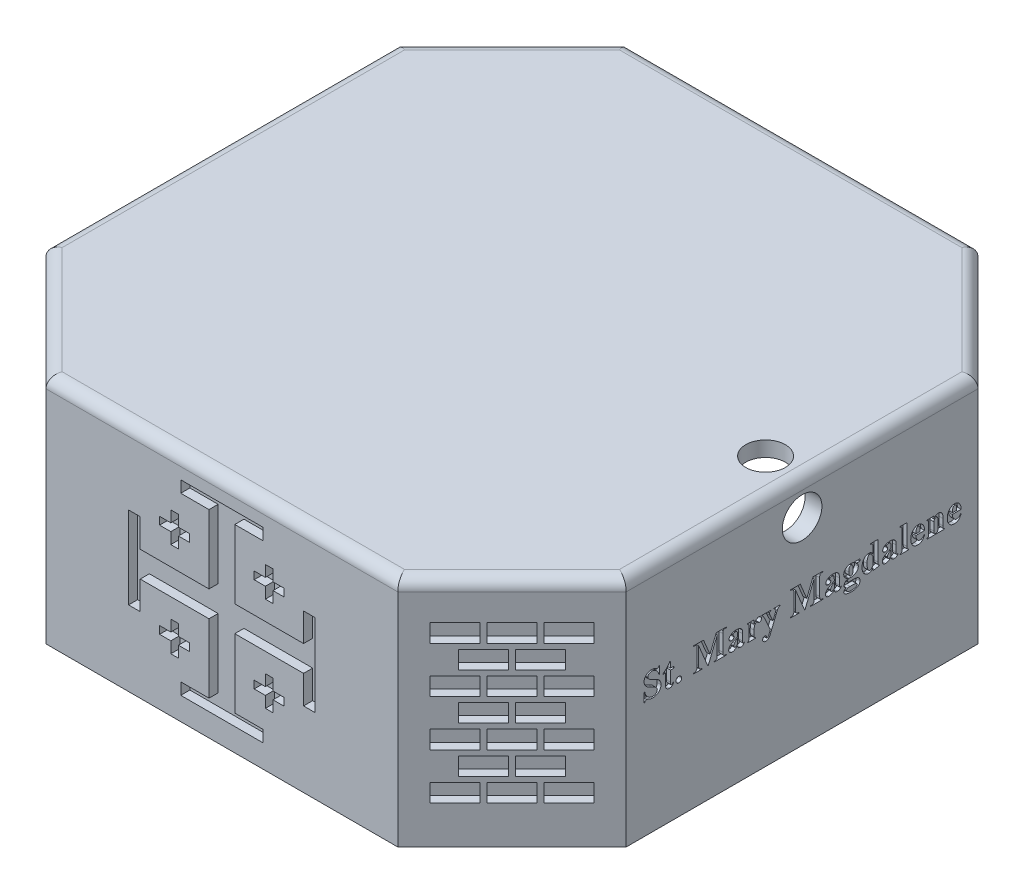
SolidWorks part; units mm, degrees
note: '?' marks a value the reader was unsure of.
ref_plane "Front Plane" through (0, 0, 0) normal (0, 0, 1) x (1, 0, 0)
ref_plane "Top Plane" through (0, 0, 0) normal (0, 1, 0) x (1, 0, 0)
ref_plane "Right Plane" through (0, 0, 0) normal (1, 0, 0) x (0, 0, -1)
sketch "Sketch1" plane through (0, 0, 0) normal (0, 1, 0) x (1, 0, 0)
  line L1 (0, 0) -> (38.1, 0)
  line L2 (0, 0) -> (0, 38.1)
  line L3 (0, 38.1) -> (38.1, 38.1)
  line L4 (38.1, 0) -> (38.1, 38.1)
  dimension "D1" = 38.1
extrude "Boss-Extrude1" add sketch "Sketch1" along normal blind 15.2575
sketch "Sketch2" plane through (0, 15.2575, 0) normal (0, 1, 0) x (1, 0, 0)
  line L0 (0, 19.05) -> (38.1, 19.05) construction
  line L1 (0, 38.1) -> (0, 0) construction
  line L2 (38.1, 0) -> (38.1, 38.1) construction
  line L15 (38.1, 30.6) -> (30.6, 38.1)
  line L33 (38.1, 7.5) -> (30.6, 0)
  line L34 (7.5, 0) -> (0, 7.5)
  line L35 (7.5, 38.1) -> (0, 30.6)
  line L36 (38.1, 7.5) -> (38.1, 0)
  line L37 (38.1, 0) -> (30.6, 0)
  line L38 (38.1, 30.6) -> (38.1, 38.1)
  line L39 (38.1, 38.1) -> (30.6, 38.1)
  line L40 (7.5, 38.1) -> (0, 38.1)
  line L41 (0, 38.1) -> (0, 30.6)
  line L42 (0, 7.5) -> (0, 0)
  line L43 (0, 0) -> (7.5, 0)
  dimension "D1" = 7.5
extrude "Cut-Extrude1" cut sketch "Sketch2" against normal through all
ref_plane "Plane1" through (30.6, 0, 0) normal (1, 0, 0) x (0, 1, 0)
ref_plane "Plane2" through (0, 0, -19.05) normal (0, 0, 1) x (1, 0, 0)
ref_plane "Plane3" through (19.05, 0, 0) normal (-1, 0, 0) x (0, 0, 1)
sketch "Sketch11" plane through (0, 0, 0) normal (0, -1, 0) x (1, 0, 0)
  line L0 (1.1, -30.1444) -> (7.9556, -37)
  line L1 (7.9556, -37) -> (30.1444, -37)
  line L2 (30.1444, -37) -> (37, -30.1444)
  line L3 (37, -30.1444) -> (37, -7.9556)
  line L4 (37, -7.9556) -> (30.1444, -1.1)
  line L5 (30.1444, -1.1) -> (7.9556, -1.1)
  line L6 (7.9556, -1.1) -> (1.1, -7.9556)
  line L7 (1.1, -7.9556) -> (1.1, -30.1444)
  line L8 (7.5, 0) -> (0, -7.5) construction
  line L10 (1.1, -19.05) -> (0, -19.05) construction
  line L11 (0, -30.6) -> (0, -7.5) construction
  line L14 (19.05, -1.1) -> (19.05, 0) construction
  line L15 (7.5, 0) -> (30.6, 0) construction
  line L18 (37, -19.05) -> (38.1, -19.05) construction
  line L19 (38.1, -7.5) -> (38.1, -30.6) construction
  line L22 (19.05, -37) -> (19.05, -38.1) construction
  line L23 (30.6, -38.1) -> (7.5, -38.1) construction
  dimension "D1" = 1.1
  dimension "D2" = 1.1
extrude "Cut-Extrude5" cut sketch "Sketch11" against normal offset from surface (14.2575 mm away) 1 up to face at (19.05, 15.2575, -19.05)
sketch "Sketch12" plane through (0, 15.2575, 0) normal (0, 1, 0) x (1, 0, 0)
  line L0 (38.1, 19.05) -> (0, 19.05) construction
  line L1 (38.1, 7.5) -> (38.1, 30.6) construction
  line L2 (0, 30.6) -> (0, 7.5) construction
  line L3 (37, 7.9556) -> (37, 30.1444) construction
  line L4 (37, 7.9556) -> (37, 30.1444) construction
  circle A0 centre (35.7, 19.05) radius 1.3
  dimension "D1" = 2.6
extrude "Cut-Extrude6" cut sketch "Sketch12" against normal through all
ref_axis "Axis1" through (19.05, 16.0204, -19.05) along (0, -1, 0)?
sketch "Sketch15" plane through (0, 0, -38.1) normal (0, 0, -1) x (-1, 0, 0)
  line L0 (-19.05, 15.2575) -> (-19.05, 0) construction
  line L1 (-30.6, 15.2575) -> (-7.5, 15.2575) construction
  line L2 (-30.6, 0) -> (-7.5, 0) construction
  line L3 (-19.05, 13.7575) -> (-21.7513, 13.7575)
  line L4 (-21.7513, 13.7575) -> (-21.7513, 12.9911)
  line L5 (-21.7513, 12.9911) -> (-19.8974, 12.9911)
  line L6 (-19.8974, 12.9911) -> (-19.8974, 8.4762)
  line L7 (-19.8974, 8.4762) -> (-24.4123, 8.4762)
  line L8 (-24.4123, 8.4762) -> (-24.4123, 10.3301)
  line L9 (-24.4123, 10.3301) -> (-25.1788, 10.3301)
  line L10 (-25.1788, 10.3301) -> (-25.1788, 7.6288)
  line L11 (-22.1549, 8.4762) -> (-22.1549, 10.7336) construction
  line L12 (-22.1549, 10.7336) -> (-19.8974, 10.7336) construction
  line L13 (-22.4049, 11.7205) -> (-21.9049, 11.7205)
  line L14 (-21.9049, 11.7205) -> (-21.9049, 10.9836)
  line L15 (-21.9049, 10.9836) -> (-21.168, 10.9836)
  line L16 (-21.168, 10.9836) -> (-21.168, 10.4836)
  line L17 (-21.9049, 9.7468) -> (-22.4049, 9.7468)
  line L18 (-21.9049, 10.4836) -> (-21.9049, 9.7468)
  line L19 (-21.168, 10.4836) -> (-21.9049, 10.4836)
  line L20 (-23.1417, 10.4836) -> (-23.1417, 10.9836)
  line L21 (-22.4049, 10.4836) -> (-23.1417, 10.4836)
  line L22 (-22.4049, 9.7468) -> (-22.4049, 10.4836)
  line L23 (-22.4049, 11.7205) -> (-21.9049, 11.7205)
  line L24 (-22.4049, 10.9836) -> (-22.4049, 11.7205)
  line L25 (-23.1417, 10.9836) -> (-22.4049, 10.9836)
  line L26 (-19.8974, 8.4762) -> (-19.05, 7.6288) construction
  line L27 (-12.9212, 7.6288) -> (-12.9212, 10.3301)
  line L28 (-12.9212, 10.3301) -> (-13.6877, 10.3301)
  line L29 (-13.6877, 10.3301) -> (-13.6877, 8.4762)
  line L30 (-13.6877, 8.4762) -> (-18.2026, 8.4762)
  line L31 (-18.2026, 8.4762) -> (-18.2026, 12.9911)
  line L32 (-18.2026, 12.9911) -> (-16.3487, 12.9911)
  line L33 (-16.3487, 12.9911) -> (-16.3487, 13.7575)
  line L34 (-16.3487, 13.7575) -> (-19.05, 13.7575)
  line L35 (-14.9583, 10.9836) -> (-14.9583, 10.4836)
  line L36 (-14.9583, 10.4836) -> (-15.6951, 10.4836)
  line L37 (-15.6951, 10.4836) -> (-15.6951, 9.7468)
  line L38 (-15.6951, 9.7468) -> (-16.1951, 9.7468)
  line L39 (-16.932, 10.4836) -> (-16.932, 10.9836)
  line L40 (-16.1951, 10.4836) -> (-16.932, 10.4836)
  line L41 (-16.1951, 9.7468) -> (-16.1951, 10.4836)
  line L42 (-16.1951, 11.7205) -> (-15.6951, 11.7205)
  line L43 (-16.1951, 10.9836) -> (-16.1951, 11.7205)
  line L44 (-16.932, 10.9836) -> (-16.1951, 10.9836)
  line L45 (-14.9583, 10.9836) -> (-14.9583, 10.4836)
  line L46 (-15.6951, 10.9836) -> (-14.9583, 10.9836)
  line L47 (-15.6951, 11.7205) -> (-15.6951, 10.9836)
  line L48 (-18.2026, 10.7336) -> (-15.9451, 10.7336) construction
  line L49 (-15.9451, 10.7336) -> (-15.9451, 8.4762) construction
  line L50 (-19.05, 1.5) -> (-16.3487, 1.5)
  line L51 (-16.3487, 1.5) -> (-16.3487, 2.2665)
  line L52 (-16.3487, 2.2665) -> (-18.2026, 2.2665)
  line L53 (-18.2026, 2.2665) -> (-18.2026, 6.7813)
  line L54 (-18.2026, 6.7813) -> (-13.6877, 6.7813)
  line L55 (-13.6877, 6.7813) -> (-13.6877, 4.9275)
  line L56 (-13.6877, 4.9275) -> (-12.9212, 4.9275)
  line L57 (-12.9212, 4.9275) -> (-12.9212, 7.6288)
  line L58 (-15.6951, 3.537) -> (-16.1951, 3.537)
  line L59 (-16.1951, 3.537) -> (-16.1951, 4.2739)
  line L60 (-16.1951, 4.2739) -> (-16.932, 4.2739)
  line L61 (-16.932, 4.2739) -> (-16.932, 4.7739)
  line L62 (-16.1951, 5.5108) -> (-15.6951, 5.5108)
  line L63 (-16.1951, 4.7739) -> (-16.1951, 5.5108)
  line L64 (-16.932, 4.7739) -> (-16.1951, 4.7739)
  line L65 (-14.9583, 4.7739) -> (-14.9583, 4.2739)
  line L66 (-15.6951, 4.7739) -> (-14.9583, 4.7739)
  line L67 (-15.6951, 5.5108) -> (-15.6951, 4.7739)
  line L68 (-15.6951, 3.537) -> (-16.1951, 3.537)
  line L69 (-15.6951, 4.2739) -> (-15.6951, 3.537)
  line L70 (-14.9583, 4.2739) -> (-15.6951, 4.2739)
  line L71 (-15.9451, 6.7813) -> (-15.9451, 4.5239) construction
  line L72 (-15.9451, 4.5239) -> (-18.2026, 4.5239) construction
  line L73 (-25.1788, 7.6288) -> (-25.1788, 4.9275)
  line L74 (-25.1788, 4.9275) -> (-24.4123, 4.9275)
  line L75 (-24.4123, 4.9275) -> (-24.4123, 6.7813)
  line L76 (-24.4123, 6.7813) -> (-19.8974, 6.7813)
  line L77 (-19.8974, 6.7813) -> (-19.8974, 2.2665)
  line L78 (-19.8974, 2.2665) -> (-21.7513, 2.2665)
  line L79 (-21.7513, 2.2665) -> (-21.7513, 1.5)
  line L80 (-21.7513, 1.5) -> (-19.05, 1.5)
  line L81 (-23.1417, 4.2739) -> (-23.1417, 4.7739)
  line L82 (-23.1417, 4.7739) -> (-22.4049, 4.7739)
  line L83 (-22.4049, 4.7739) -> (-22.4049, 5.5108)
  line L84 (-22.4049, 5.5108) -> (-21.9049, 5.5108)
  line L85 (-21.168, 4.7739) -> (-21.168, 4.2739)
  line L86 (-21.9049, 4.7739) -> (-21.168, 4.7739)
  line L87 (-21.9049, 5.5108) -> (-21.9049, 4.7739)
  line L88 (-21.9049, 3.537) -> (-22.4049, 3.537)
  line L89 (-21.9049, 4.2739) -> (-21.9049, 3.537)
  line L90 (-21.168, 4.2739) -> (-21.9049, 4.2739)
  line L91 (-23.1417, 4.2739) -> (-23.1417, 4.7739)
  line L92 (-22.4049, 4.2739) -> (-23.1417, 4.2739)
  line L93 (-22.4049, 3.537) -> (-22.4049, 4.2739)
  line L94 (-19.8974, 4.5239) -> (-22.1549, 4.5239) construction
  line L95 (-22.1549, 4.5239) -> (-22.1549, 6.7813) construction
  point P24 (-21.168, 10.7336)
  point P25 (-22.1549, 11.7205)
  point P26 (-19.05, 7.6288)
  point P40 (-22.1549, 10.7336)
  point P57 (-15.9451, 9.7468)
  point P58 (-14.9583, 10.7336)
  point P68 (-15.9451, 10.7336)
  point P86 (-16.932, 4.5239)
  point P87 (-15.9451, 3.537)
  point P97 (-15.9451, 4.5239)
  point P115 (-22.1549, 5.5108)
  point P116 (-23.1417, 4.5239)
  point P126 (-22.1549, 4.5239)
  point P127 (-19.05, 7.6288)
  dimension "D1" = 45
  dimension "D3" = 0.5
  dimension "D4" = 1.5
  dimension "D5" = 1.5
  dimension "D2" = 4
extrude "Cut-Extrude9" cut sketch "Sketch15" against normal blind 0.6 contours L79 L80 L50 L51 L52 L53 L54 L55 L56 L57 L27 L28 L29 L30 L31 L32 L33 L34 L3 L4 L5 L6 L7 L8 L9 L10 L73 L74 L75 L76 L77 L78 | L25 L20 L21 L22 L17 L18 L19 L16 L15 L14 L13 L24 | L47 L42 L43 L44 L39 L40 L41 L38 L37 L36 L35 L46 | L70 L65 L66 L67 L62 L63 L64 L61 L60 L59 L58 L69 | L93 L88 L89 L90 L85 L86 L87 L84 L83 L82 L81 L92
mirror "Mirror3" about plane through (0, 0, -19.05) normal (0, 0, 1) of "Cut-Extrude9"
sketch "Sketch16" plane through (38.1, 0, 0) normal (1, 0, 0) x (0, 0, -1)
  line L0 (7.5, 7.6288) -> (30.6, 7.6288) construction
  line L1 (7.5, 0) -> (7.5, 15.2575) construction
  line L2 (30.6, 0) -> (30.6, 15.2575) construction
  text T0 "St. Mary Magdalene" font "Times New Roman" height 1.6
extrude "Cut-Extrude10" cut sketch "Sketch16" against normal blind 0.25
sketch "Sketch17" plane through (0, 0, 0) normal (-1, 0, 0) x (0, 0, 1)
  line L0 (-19.05, 0) -> (-19.05, 15.2575) construction
  line L1 (-30.6, 0) -> (-7.5, 0) construction
  line L2 (-30.6, 15.2575) -> (-7.5, 15.2575) construction
  line L3 (-18.0272, 12.7575) -> (-20.0728, 12.7575)
  line L4 (-20.0728, 12.7575) -> (-20.0728, 11.5984)
  line L5 (-20.0728, 11.5984) -> (-21.0857, 11.5984)
  line L6 (-21.0857, 11.5984) -> (-21.0857, 12.7575)
  line L7 (-21.0857, 12.7575) -> (-22.3904, 12.7575)
  line L8 (-22.3904, 12.7575) -> (-22.3904, 9.9341)
  line L9 (-22.3904, 9.9341) -> (-20.7476, 9.9341)
  line L10 (-20.7476, 9.9341) -> (-21.6155, 4.1643)
  line L11 (-21.6155, 4.1643) -> (-23.3564, 4.1643)
  line L12 (-23.3564, 4.1643) -> (-23.3564, 2.5)
  line L13 (-23.3564, 2.5) -> (-14.7436, 2.5)
  line L14 (-30.6, 12.7575) -> (-7.5, 12.7575) construction
  line L15 (-30.6, 0) -> (-30.6, 15.2575) construction
  line L16 (-7.5, 0) -> (-7.5, 15.2575) construction
  line L17 (-30.6, 2.5) -> (-7.5, 2.5) construction
  line L20 (-18.0272, 12.7575) -> (-18.0272, 11.5984)
  line L21 (-17.0143, 11.5984) -> (-17.0143, 12.7575)
  line L22 (-18.0272, 11.5984) -> (-17.0143, 11.5984)
  line L23 (-17.0143, 12.7575) -> (-15.7096, 12.7575)
  line L24 (-15.7096, 12.7575) -> (-15.7096, 9.9341)
  line L25 (-15.7096, 9.9341) -> (-17.3524, 9.9341)
  line L26 (-17.3524, 9.9341) -> (-16.4845, 4.1643)
  line L27 (-14.7436, 4.1643) -> (-14.7436, 2.5)
  line L28 (-16.4845, 4.1643) -> (-14.7436, 4.1643)
  line L29 (-17.3524, 9.9341) -> (-17.3524, 11.5984) construction
  line L30 (-17.3524, 11.5984) -> (-17.0143, 11.5984) construction
  point P31 (-19.05, 12.7575)
  point P42 (-19.05, 2.5)
  dimension "D1" = 2.5
  dimension "D2" = 2.5
extrude "Cut-Extrude11" cut sketch "Sketch17" against normal blind 0.6
sketch "Sketch18" plane through (-15.3, 0, -15.3) normal (-0.7071, 0, -0.7071) x (-0.7071, 0, 0.7071)
  line L0 (-28.4361, 3.6728) -> (-28.0948, 3.6728) construction
  line L1 (-30.7441, 3.6728) -> (-28.4361, 3.6728)
  line L2 (-30.7441, 3.6728) -> (-30.7441, 2.5)
  line L3 (-30.7441, 2.5) -> (-28.4361, 2.5)
  line L4 (-28.4361, 3.6728) -> (-28.4361, 2.5)
  line L5 (-28.4361, 3.6728) -> (-28.4361, 4.0141) construction
  line L6 (-32.2441, 2.5) -> (-21.6375, 2.5) construction
  line L7 (-32.2441, 0) -> (-32.2441, 15.2575) construction
  line L8 (-21.6375, 0) -> (-21.6375, 15.2575) construction
  line L9 (-32.2441, 12.7575) -> (-21.6375, 12.7575) construction
  line L10 (-32.2441, 15.2575) -> (-21.6375, 15.2575) construction
  line L11 (-32.2441, 0) -> (-21.6375, 0) construction
  line L12 (-30.7441, 0) -> (-30.7441, 15.2575) construction
  line L13 (-23.1375, 15.2575) -> (-23.1375, 0) construction
  line L14 (-28.0948, 3.6728) -> (-25.7868, 3.6728)
  line L15 (-28.0948, 3.6728) -> (-28.0948, 2.5)
  line L16 (-28.0948, 2.5) -> (-25.7868, 2.5)
  line L17 (-25.7868, 3.6728) -> (-25.7868, 2.5)
  line L18 (-25.7868, 3.6728) -> (-25.4454, 3.6728) construction
  line L19 (-25.7868, 3.6728) -> (-25.7868, 4.0141) construction
  line L20 (-25.4454, 3.6728) -> (-23.1375, 3.6728)
  line L21 (-25.4454, 3.6728) -> (-25.4454, 2.5)
  line L22 (-25.4454, 2.5) -> (-23.1375, 2.5)
  line L23 (-23.1375, 3.6728) -> (-23.1375, 2.5)
  line L24 (-23.1375, 3.6728) -> (-22.7961, 3.6728) construction
  line L25 (-23.1375, 3.6728) -> (-23.1375, 4.0141) construction
  line L26 (-25.6161, 3.6728) -> (-25.6161, 4.0141) construction
  line L27 (-29.4194, 5.1869) -> (-27.1114, 5.1869)
  line L28 (-29.4194, 5.1869) -> (-29.4194, 4.0141)
  line L29 (-29.4194, 4.0141) -> (-27.1114, 4.0141)
  line L30 (-27.1114, 5.1869) -> (-27.1114, 4.0141)
  line L31 (-26.7701, 5.1869) -> (-24.4621, 5.1869)
  line L32 (-26.7701, 5.1869) -> (-26.7701, 4.0141)
  line L33 (-26.7701, 4.0141) -> (-24.4621, 4.0141)
  line L34 (-24.4621, 5.1869) -> (-24.4621, 4.0141)
  line L35 (-28.2654, 3.6728) -> (-28.2654, 4.0141) construction
  line L36 (-27.1114, 5.1869) -> (-26.7701, 5.1869) construction
  line L37 (-30.7441, 6.701) -> (-28.4361, 6.701)
  line L38 (-30.7441, 6.701) -> (-30.7441, 5.5283)
  line L39 (-30.7441, 5.5283) -> (-28.4361, 5.5283)
  line L40 (-28.4361, 6.701) -> (-28.4361, 5.5283)
  line L41 (-28.0948, 6.701) -> (-25.7868, 6.701)
  line L42 (-28.0948, 6.701) -> (-28.0948, 5.5283)
  line L43 (-28.0948, 5.5283) -> (-25.7868, 5.5283)
  line L44 (-25.7868, 6.701) -> (-25.7868, 5.5283)
  line L45 (-25.4454, 6.701) -> (-23.1375, 6.701)
  line L46 (-25.4454, 6.701) -> (-25.4454, 5.5283)
  line L47 (-25.4454, 5.5283) -> (-23.1375, 5.5283)
  line L48 (-23.1375, 6.701) -> (-23.1375, 5.5283)
  line L49 (-28.4361, 6.701) -> (-28.0948, 6.701) construction
  line L50 (-25.7868, 6.701) -> (-25.4454, 6.701) construction
  line L51 (-30.7441, 9.7293) -> (-28.4361, 9.7293)
  line L52 (-30.7441, 9.7293) -> (-30.7441, 8.5565)
  line L53 (-30.7441, 8.5565) -> (-28.4361, 8.5565)
  line L54 (-28.4361, 9.7293) -> (-28.4361, 8.5565)
  line L55 (-28.0948, 9.7293) -> (-25.7868, 9.7293)
  line L56 (-28.0948, 9.7293) -> (-28.0948, 8.5565)
  line L57 (-28.0948, 8.5565) -> (-25.7868, 8.5565)
  line L58 (-25.7868, 9.7293) -> (-25.7868, 8.5565)
  line L59 (-25.4454, 9.7293) -> (-23.1375, 9.7293)
  line L60 (-25.4454, 9.7293) -> (-25.4454, 8.5565)
  line L61 (-25.4454, 8.5565) -> (-23.1375, 8.5565)
  line L62 (-23.1375, 9.7293) -> (-23.1375, 8.5565)
  line L63 (-28.4361, 9.7293) -> (-28.0948, 9.7293) construction
  line L64 (-25.7868, 9.7293) -> (-25.4454, 9.7293) construction
  line L65 (-30.7441, 12.7575) -> (-28.4361, 12.7575)
  line L66 (-30.7441, 12.7575) -> (-30.7441, 11.5848)
  line L67 (-30.7441, 11.5848) -> (-28.4361, 11.5848)
  line L68 (-28.4361, 12.7575) -> (-28.4361, 11.5848)
  line L69 (-28.0948, 12.7575) -> (-25.7868, 12.7575)
  line L70 (-28.0948, 12.7575) -> (-28.0948, 11.5848)
  line L71 (-28.0948, 11.5848) -> (-25.7868, 11.5848)
  line L72 (-25.7868, 12.7575) -> (-25.7868, 11.5848)
  line L73 (-25.4454, 12.7575) -> (-23.1375, 12.7575)
  line L74 (-25.4454, 12.7575) -> (-25.4454, 11.5848)
  line L75 (-25.4454, 11.5848) -> (-23.1375, 11.5848)
  line L76 (-23.1375, 12.7575) -> (-23.1375, 11.5848)
  line L77 (-28.4361, 12.7575) -> (-28.0948, 12.7575) construction
  line L78 (-25.7868, 12.7575) -> (-25.4454, 12.7575) construction
  line L79 (-27.1114, 8.2152) -> (-27.1114, 7.0424)
  line L80 (-29.4194, 8.2152) -> (-29.4194, 7.0424)
  line L81 (-29.4194, 8.2152) -> (-27.1114, 8.2152)
  line L82 (-29.4194, 7.0424) -> (-27.1114, 7.0424)
  line L83 (-26.7701, 7.0424) -> (-24.4621, 7.0424)
  line L84 (-24.4621, 8.2152) -> (-24.4621, 7.0424)
  line L85 (-26.7701, 8.2152) -> (-24.4621, 8.2152)
  line L86 (-26.7701, 8.2152) -> (-26.7701, 7.0424)
  line L87 (-27.1114, 11.2434) -> (-27.1114, 10.0706)
  line L88 (-29.4194, 11.2434) -> (-29.4194, 10.0706)
  line L89 (-29.4194, 11.2434) -> (-27.1114, 11.2434)
  line L90 (-29.4194, 10.0706) -> (-27.1114, 10.0706)
  line L91 (-26.7701, 10.0706) -> (-24.4621, 10.0706)
  line L92 (-24.4621, 11.2434) -> (-24.4621, 10.0706)
  line L93 (-26.7701, 11.2434) -> (-24.4621, 11.2434)
  line L94 (-26.7701, 11.2434) -> (-26.7701, 10.0706)
  line L95 (-25.7868, 6.701) -> (-25.7868, 7.0424) construction
  line L96 (-26.7701, 5.1869) -> (-26.7701, 5.5283) construction
  dimension "D1" = 2.5
  dimension "D2" = 2.5
  dimension "D3" = 1.5
  dimension "D4" = 1.5
  dimension "D6" = 4
  dimension "D7" = 3
  dimension "D5" = 3
extrude "Cut-Extrude12" cut sketch "Sketch18" against normal blind 0.6
mirror "Mirror4" about plane through (0, 0, -19.05) normal (0, 0, 1) of "Cut-Extrude12"
mirror "Mirror5" about plane through (19.05, 0, 0) normal (-1, 0, 0) of "Mirror4", "Cut-Extrude12"
fillet "Fillet1" radius 0.25 1 edges at (0, 2.5, -19.05) conic rho 0.05
fillet "Fillet2" radius 0.75 8 edges at (19.05, 15.2575, 0) (3.75, 15.2575, -3.75) (0, 15.2575, -19.05) (3.75, 15.2575, -34.35) (19.05, 15.2575, -38.1) (34.35, 15.2575, -34.35) (38.1, 15.2575, -19.05) (34.35, 15.2575, -3.75)
sketch "Sketch20" plane through (38.1, 0, 0) normal (1, 0, 0) x (0, 0, -1)
  line L0 (30.1444, 14.2575) -> (7.9556, 14.2575) construction
  line L1 (30.1444, 14.2575) -> (7.9556, 14.2575) construction
  line L2 (19.05, 14.2575) -> (19.05, 12.9575) construction
  circle A0 centre (19.05, 12.9575) radius 1.3
  dimension "D1" = 2.6
extrude "Cut-Extrude13" cut sketch "Sketch20" against normal up to surface (1.1 mm away) up to face at (37, 8.5545, -19.05)
